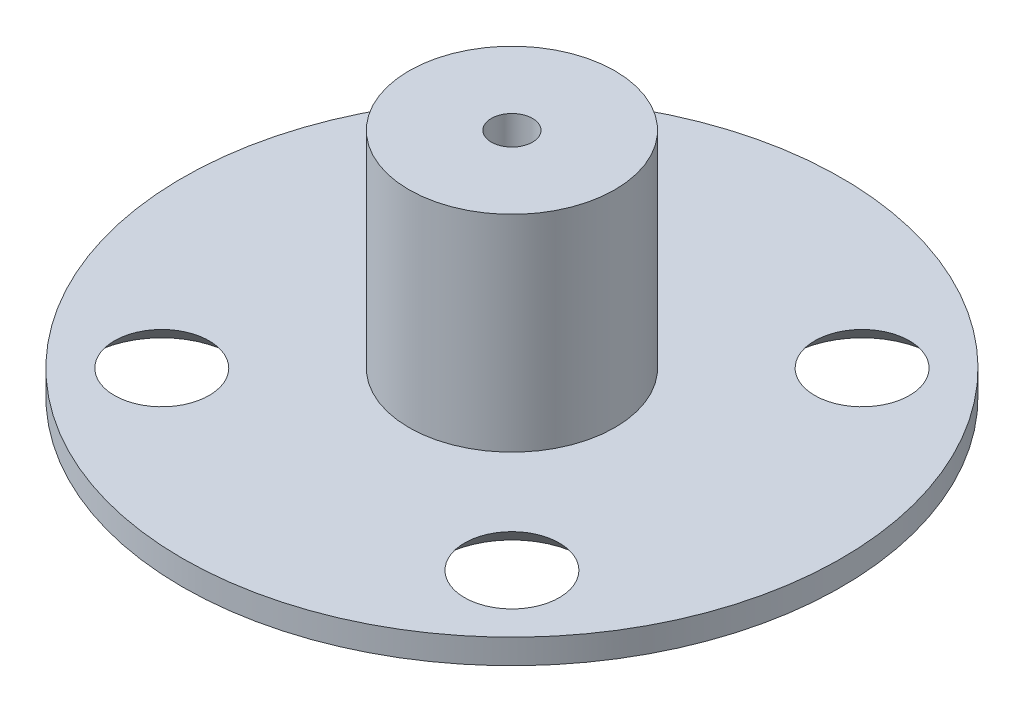
SolidWorks part; units mm, degrees
material "PLA"
ref_plane "Front" through (0, 0, 0) normal (0, 0, 1) x (1, 0, 0)
ref_plane "Top" through (0, 0, 0) normal (0, 1, 0) x (1, 0, 0)
ref_plane "Right" through (0, 0, 0) normal (1, 0, 0) x (0, 0, -1)
other "Configuration Table"
sketch "Esquisse1" plane through (0, 0, 0) normal (0, 1, 0) x (1, 0, 0)
  line L1 (-4.25, 4.25) -> (4.25, 4.25) construction
  line L2 (-4.25, 4.25) -> (-4.25, -4.25) construction
  line L3 (-4.25, -4.25) -> (4.25, -4.25) construction
  line L4 (4.25, 4.25) -> (4.25, -4.25) construction
  line L5 (-4.25, 4.25) -> (4.25, -4.25) construction
  line L6 (-4.25, -4.25) -> (4.25, 4.25) construction
  circle A0 centre (-4.25, 4.25) radius 1
  circle A1 centre (4.25, 4.25) radius 1
  circle A2 centre (4.25, -4.25) radius 1
  circle A3 centre (-4.25, -4.25) radius 1
  circle A4 centre (0, 0) radius 8
  point P0 (0, 0)
  dimension "D2" = 2
  dimension "D3" = 16
  dimension "D1" = 8.5
extrude "Boss.-Extru.1" add sketch "Esquisse1" along normal blind 0.6
sketch "Esquisse2" plane through (0, 0.6, 0) normal (0, 1, 0) x (1, 0, 0)
  circle A0 centre (0, 0) radius 2.5
  dimension "D1" = 5
extrude "Boss.-Extru.2" add sketch "Esquisse2" along normal blind 5
sketch "Esquisse3" plane through (0, 5.6, 0) normal (0, 1, 0) x (1, 0, 0)
  circle A0 centre (0, 0) radius 0.5
  dimension "D1" = 1
extrude "Enlèv. mat.-Extru.1" cut sketch "Esquisse3" against normal up to surface (5.6 mm away) up to face at (0, 0, 8)
chamfer "Chanfrein1" distance 0.75 angle 45 4 edges at (4.25, 0, 5.25) (-4.25, 0, 5.25) (-4.25, 0, -3.25) (4.25, 0, -3.25)
